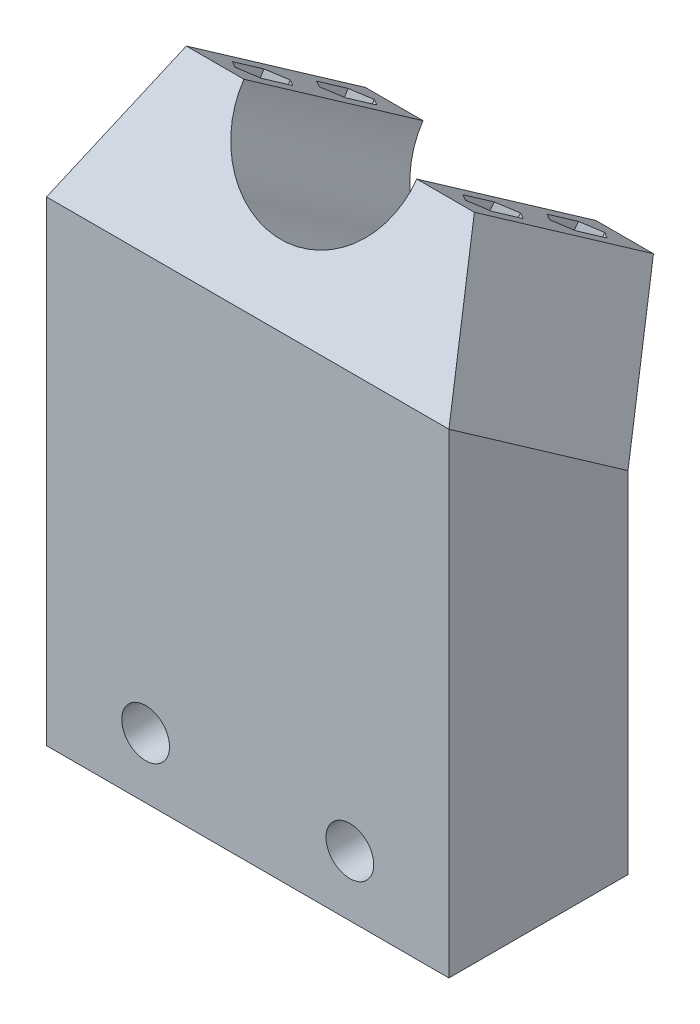
SolidWorks part; units mm, degrees
ref_plane "Alzado" through (0, 0, 0) normal (0, 0, 1) x (1, 0, 0)
ref_plane "Planta" through (0, 0, 0) normal (0, 1, 0) x (1, 0, 0)
ref_plane "Vista lateral" through (0, 0, 0) normal (1, 0, 0) x (0, 0, -1)
sketch "Croquis1" plane through (0, 0, 0) normal (0, 0, 1) x (1, 0, 0)
  line L0 (20.955, 0) -> (20.955, 6.2992) construction
  line L1 (0, 0) -> (41.91, 0)
  line L2 (0, 0) -> (0, 36.4389)
  line L3 (0, 36.4389) -> (41.91, 36.4389)
  line L4 (41.91, 0) -> (41.91, 36.4389)
  circle A0 centre (10.3187, 6.2992) radius 2.4892
  circle A1 centre (31.5912, 6.2992) radius 2.4892
  dimension "D1" = 4.9784
  dimension "D2" = 10.3187
  dimension "D3" = 3.81
  dimension "D4" = 32.6289
  dimension "D5" = 41.91
extrude "Saliente-Extruir1" add sketch "Croquis1" along normal blind 18.6531
sketch "Croquis3" plane through (0, 0, 0) normal (-1, 0, 0) x (0, 0, 1)
  line L0 (0, 36.4389) -> (18.6531, 49.4999)
  line L1 (0, 36.4389) -> (-7.8285, 47.6192) construction
  line L2 (18.6531, 49.4999) -> (18.6531, 36.4389)
  line L3 (0, 36.4389) -> (18.6531, 36.4389)
  dimension "D1" = 35
ref_plane "Plano2" through (0, 11.988, 17.1207) normal (0, 0.5736, 0.8192) x (1, 0, 0)
extrude "Saliente-Extruir2" add sketch "Croquis3" against normal up to vertex (41.91 mm away) up to point (41.91, 36.4389, 0)
sketch "Croquis5" plane through (0, 11.988, 17.1207) normal (0, 0.5736, 0.8192) x (1, 0, 0)
  line L0 (20.955, 29.849) -> (20.955, 44.849) construction
  line L1 (41.91, 29.849) -> (0, 29.849) construction
  line L2 (5.955, 44.849) -> (11.955, 44.849)
  line L3 (11.955, 44.849) -> (29.955, 44.849)
  line L4 (29.955, 44.849) -> (35.955, 44.849)
  line L5 (5.955, 44.849) -> (0, 29.849)
  line L6 (0, 29.849) -> (41.91, 29.849)
  line L7 (41.91, 29.849) -> (35.955, 44.849)
  circle A0 centre (20.955, 44.849) radius 15
  circle A1 centre (20.955, 44.849) radius 9
  dimension "D1" = 18
  dimension "D2" = 6
extrude "Saliente-Extruir3" add sketch "Croquis5" along normal up to vertex (22.7713 mm away) separate body contours A0 L0 A1 L2 | L0 A0 L4 A1 | A0 L5 L6 | A0 L6 L7 region at (13.1564, 42.3379, -4.1306) region at (35.1683, 39.8327, -2.3764) region at (6.7417, 39.8327, -2.3764) region at (28.7536, 42.3379, -4.1306) up to point (0, 49.4999, 18.6531)
sketch "Croquis7" plane through (0, 36.7381, -25.7243) normal (0, 0.8192, -0.5736) x (1, 0, 0)
  line L0 (8.955, -20.9005) -> (8.955, -23.4405) construction
  line L1 (7.455, -28.9405) -> (7.455, -24.9405)
  line L2 (10.455, -28.9405) -> (10.455, -24.9405)
  line L3 (7.455, -28.9405) -> (8.955, -30.4405)
  line L4 (8.955, -30.4405) -> (10.455, -28.9405)
  line L5 (10.455, -24.9405) -> (8.955, -23.4405)
  line L6 (8.955, -23.4405) -> (7.455, -24.9405)
  line L7 (5.955, -20.9005) -> (11.955, -20.9005) construction
  line L8 (5.955, -32.2861) -> (11.7793, -32.2861) construction
  line L9 (5.955, -43.6717) -> (5.955, -20.9005) construction
  line L10 (8.955, -41.1317) -> (7.455, -39.6317)
  line L11 (10.455, -39.6317) -> (8.955, -41.1317)
  line L12 (8.955, -34.1317) -> (10.455, -35.6317)
  line L13 (7.455, -35.6317) -> (8.955, -34.1317)
  line L14 (10.455, -35.6317) -> (10.455, -39.6317)
  line L15 (7.455, -35.6317) -> (7.455, -39.6317)
  line L16 (11.955, -43.6717) -> (29.955, -43.6717) construction
  line L17 (11.955, -43.6717) -> (29.955, -43.6717) construction
  line L18 (20.955, -43.6717) -> (20.955, -38.4515) construction
  point P2 (11.3797, -24.6032)
  point P10 (11.3797, -39.969)
  dimension "D1" = 4
  dimension "D2" = 3
  dimension "D3" = 2.54
revolve "Cortar-Revolución1" cut sketch "Croquis7" angle 360 about L18
